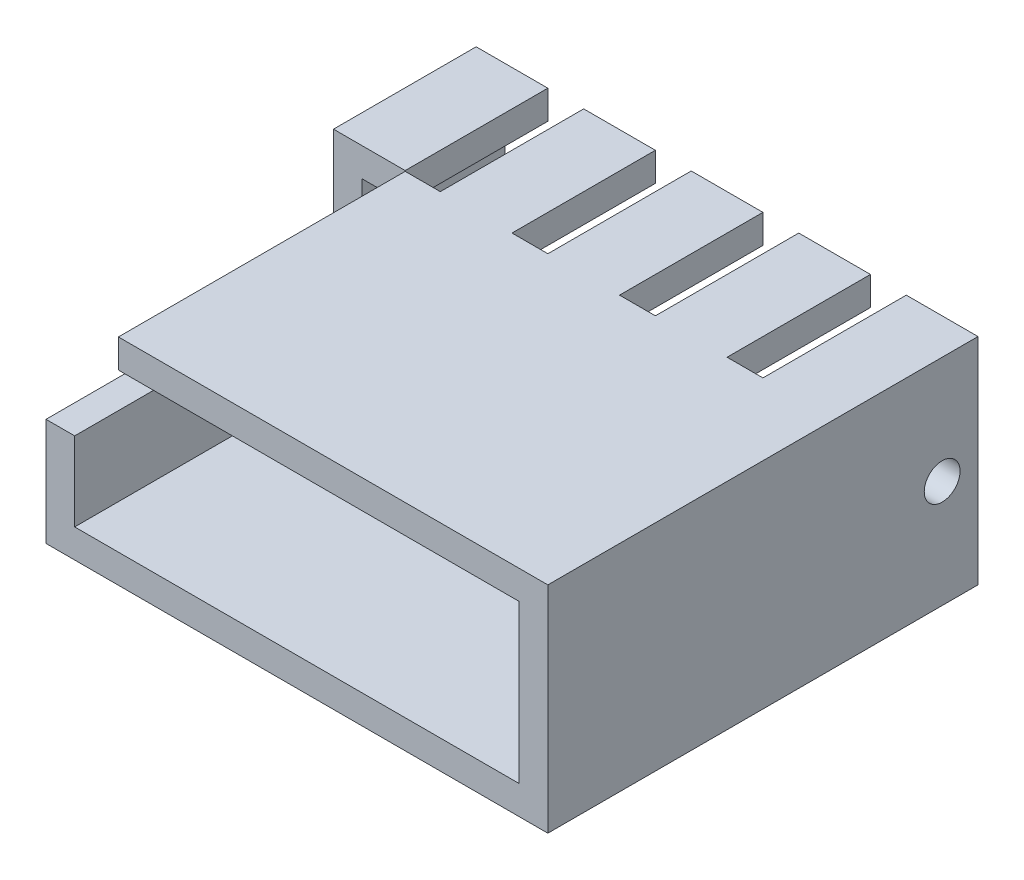
SolidWorks part; units mm, degrees
ref_plane "Front Plane" through (0, 0, 0) normal (0, 0, 1) x (1, 0, 0)
ref_plane "Top Plane" through (0, 0, 0) normal (0, 1, 0) x (1, 0, 0)
ref_plane "Right Plane" through (0, 0, 0) normal (1, 0, 0) x (0, 0, -1)
sketch "Sketch1" plane through (0, 0, 0) normal (0, 1, 0) x (1, 0, 0)
  line L1 (0, 0) -> (88.9, 0)
  line L2 (0, 0) -> (0, 76.2)
  line L3 (0, 76.2) -> (88.9, 76.2)
  line L4 (88.9, 0) -> (88.9, 76.2)
  dimension "D1" = 76.2
  dimension "D2" = 88.9
extrude "Boss-Extrude1" add sketch "Sketch1" along normal blind 38.1 contours L1 L4 L3 L2
shell "Shell1" thickness 5.08 removed face at (44.45, 19.05, -76.2) removed face at (44.45, 19.05, 0)
sketch "Sketch4" plane through (0, 0, 0) normal (0, -1, 0) x (1, 0, 0)
  line L1 (0, 0) -> (12.827, 0)
  line L2 (0, 0) -> (0, -50.927)
  line L3 (0, -50.927) -> (12.827, -50.927)
  line L4 (12.827, 0) -> (12.827, -50.927)
  dimension "D1" = 50.927
  dimension "D2" = 12.827
extrude "Cut-Extrude3" cut sketch "Sketch4" against normal through all from offset 19.05 offset against normal yes
sketch "Sketch5" plane through (0, 38.1, 0) normal (0, 1, 0) x (1, 0, 0)
  line L0 (0, 76.2) -> (88.9, 76.2) construction
  line L1 (12.7, 76.2) -> (19.05, 76.2)
  line L2 (12.7, 76.2) -> (12.7, 50.8)
  line L3 (12.7, 50.8) -> (19.05, 50.8)
  line L4 (19.05, 76.2) -> (19.05, 50.8)
  line L5 (31.75, 76.2) -> (31.75, 50.8)
  line L6 (31.75, 76.2) -> (38.1, 76.2)
  line L7 (38.1, 76.2) -> (38.1, 50.8)
  line L8 (31.75, 50.8) -> (38.1, 50.8)
  line L9 (50.8, 76.2) -> (50.8, 50.8)
  line L10 (50.8, 76.2) -> (57.15, 76.2)
  line L11 (57.15, 76.2) -> (57.15, 50.8)
  line L12 (50.8, 50.8) -> (57.15, 50.8)
  line L13 (69.85, 76.2) -> (69.85, 50.8)
  line L14 (69.85, 76.2) -> (76.2, 76.2)
  line L15 (76.2, 76.2) -> (76.2, 50.8)
  line L16 (69.85, 50.8) -> (76.2, 50.8)
  line L17 (12.7, 63.5) -> (76.2, 63.5) construction
  line L19 (12.7, 76.2) -> (5.08, 76.2) construction
  line L20 (0, 50.927) -> (0, 76.2) construction
  line L21 (76.2, 76.2) -> (83.82, 76.2) construction
  line L22 (88.9, 0) -> (88.9, 76.2) construction
  dimension "D1" = 25.4
  dimension "D2" = 6.35
  dimension "D4" = 5.08
  dimension "D5" = 5.08
  dimension "D6" = 63.5
  dimension "D3" = 4
extrude "Cut-Extrude4" cut sketch "Sketch5" against normal through all
sketch "Sketch6" plane through (0, 0, 0) normal (-1, 0, 0) x (0, 0, 1)
  line L0 (-76.2, 38.1) -> (-76.2, 0) construction
  circle A0 centre (-69.85, 19.05) radius 3.175
  point P4 (0, 0)
  point P5 (0, 0)
  point P6 (-76.2, 19.05)
  dimension "D1" = 6.35
  dimension "0.25" = 6.35
extrude "Cut-Extrude5" cut sketch "Sketch6" against normal through all and the other way blind 4.2672
